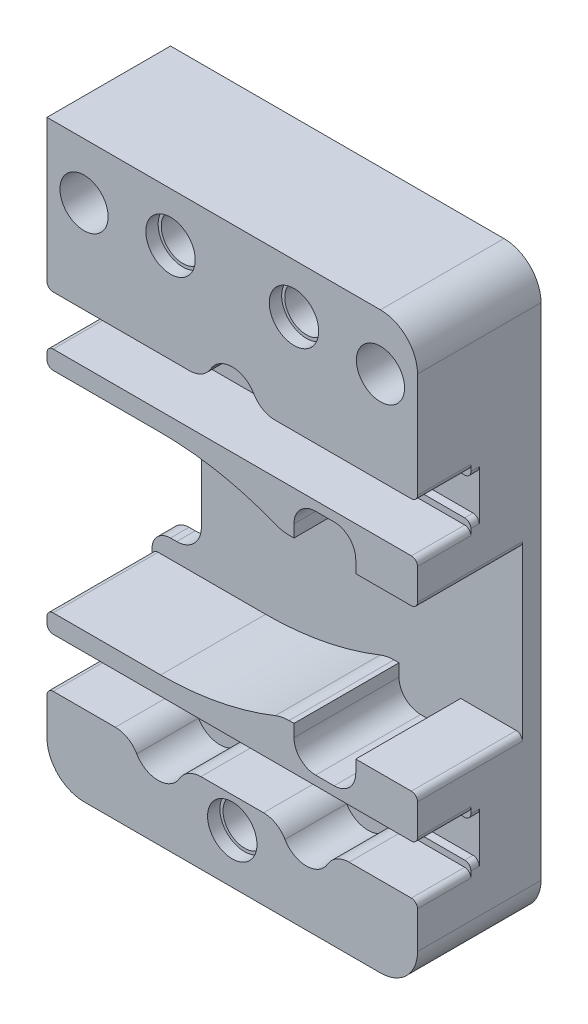
SolidWorks part; units mm, degrees
ref_plane "Front Plane" through (0, 0, 0) normal (0, 0, 1) x (1, 0, 0)
ref_plane "Top Plane" through (0, 0, 0) normal (0, 1, 0) x (1, 0, 0)
ref_plane "Right Plane" through (0, 0, 0) normal (1, 0, 0) x (0, 0, -1)
sketch "Sketch6" plane through (0, 0, 0) normal (0, 0, 1) x (1, 0, 0)
  line L1 (0, 0) -> (-30, 0)
  line L2 (0, 0) -> (0, 46.5)
  line L3 (0, 46.5) -> (-30, 46.5)
  line L4 (-30, 0) -> (-30, 46.5)
  dimension "D1" = 30
  dimension "D2" = 46.5
extrude "Boss-Extrude3" add sketch "Sketch6" along normal blind 10
sketch "Sketch7" plane through (0, 0, 0) normal (0, 0, 1) x (1, 0, 0)
  line L0 (-30, 0) -> (0, 0) construction
  line L1 (-50.5273, 13.5) -> (-28, 13.5)
  line L2 (-50.5273, 13.5) -> (-50.5273, 27.5)
  line L3 (-50.5273, 27.5) -> (-28, 27.5)
  line L4 (-26, 15.5) -> (-26, 25.5)
  line L6 (-30, 46.5) -> (-30, 0) construction
  arc A0 (-28, 13.5) -> (-26, 15.5) centre (-28, 15.5) ccw
  arc A1 (-28, 27.5) -> (-26, 25.5) centre (-28, 25.5) cw
  dimension "D1" = 2
  dimension "D5" = 2
  dimension "D2" = 13.5
  dimension "D3" = 4
  dimension "D4" = 14
extrude "Cut-Extrude2" cut sketch "Sketch7" along normal through all
sketch "Sketch9" plane through (0, 0, 10) normal (0, 0, 1) x (1, 0, 0)
  line L0 (-27, 42) -> (-3, 42) construction
  line L2 (-30, 0) -> (0, 0) construction
  line L3 (0, 46.5) -> (-30, 46.5) construction
  line L5 (-20, 42.5) -> (-10, 42.5) construction
  circle A0 centre (-10, 42.5) radius 4 construction
  circle A1 centre (-15, 4) radius 1.75 construction
  circle A2 centre (-3, 42) radius 1.95
  circle A3 centre (-27, 42) radius 1.95
  circle A4 centre (-15, 4) radius 2 construction
  circle A5 centre (-20, 42.5) radius 1.75 construction
  circle A6 centre (-10, 42.5) radius 1.75 construction
  circle A7 centre (-20, 42.5) radius 4 construction
  point P1 (-15, 42)
  point P7 (-15, 0)
  point P20 (-15, 46.5)
  point P24 (-15, 42.5)
  dimension "D1" = 3.9
  dimension "D4" = 3.5
  dimension "D6" = 4
  dimension "D8" = 8
  dimension "D2" = 42
  dimension "D3" = 24
  dimension "D5" = 4
  dimension "D7" = 10
  dimension "D9" = 4
extrude "Cut-Extrude4" cut sketch "Sketch9" against normal offset from surface (9 mm away) 1 up to face at (-22.7172, 21.6, 0)
fillet "Fillet1" radius 1.5 2 edges at (-30, 13.5, 5) (-30, 27.5, 5)
sketch "Sketch33" plane through (0, 0, 10) normal (0, 0, 1) x (1, 0, 0)
  line L0 (0, 0) -> (0, 46.5) construction
  line L1 (0, 34.5) -> (-11.5359, 34.5)
  line L2 (0, 34.5) -> (0, 30.5)
  line L3 (0, 30.5) -> (-30, 30.5)
  line L4 (-30, 34.5) -> (-30, 30.5)
  line L5 (-30, 46.5) -> (-30, 29) construction
  line L6 (-30, 12) -> (-30, 0) construction
  line L7 (0, 46.5) -> (-30, 46.5) construction
  line L8 (-30, 10.5) -> (-30, 6.5)
  line L9 (-18.4641, 34.5) -> (-30, 34.5)
  line L10 (0, 10.5) -> (0, 6.5)
  line L11 (-17.5359, 6.5) -> (-12.4641, 6.5)
  line L12 (-5.5359, 6.5) -> (0, 6.5)
  line L24 (0, 20.5) -> (-33.7301, 20.5) construction
  line L26 (-30, 6.5) -> (-24.4641, 6.5)
  line L27 (-30, 10.5) -> (0, 10.5)
  line L36 (-26, 15.5) -> (-26, 25.5) construction
  arc A0 (-13.2679, 35.5) -> (-16.7321, 35.5) centre (-15, 34.5) ccw
  arc A1 (-10.7321, 5.5) -> (-7.2679, 5.5) centre (-9, 6.5) ccw
  arc A2 (-13.2679, 35.5) -> (-11.5359, 34.5) centre (-11.5359, 36.5) ccw
  arc A3 (-16.7321, 35.5) -> (-18.4641, 34.5) centre (-18.4641, 36.5) cw
  arc A4 (-7.2679, 5.5) -> (-5.5359, 6.5) centre (-5.5359, 4.5) cw
  arc A5 (-10.7321, 5.5) -> (-12.4641, 6.5) centre (-12.4641, 4.5) ccw
  arc A6 (-17.5359, 6.5) -> (-19.2679, 5.5) centre (-17.5359, 4.5) ccw
  arc A7 (-24.4641, 6.5) -> (-22.7321, 5.5) centre (-24.4641, 4.5) cw
  arc A8 (-19.2679, 5.5) -> (-22.7321, 5.5) centre (-21, 6.5) cw
  point P14 (-30, 32.5)
  point P15 (-30, 8.5)
  point P17 (-15, 46.5)
  point P26 (-11.8223, 34.5)
  point P45 (-15, 6.5)
  point P49 (-26, 20.5)
  dimension "D5" = 2
  dimension "D4" = 2
  dimension "D6" = 2
  dimension "D1" = 12
  dimension "D2" = 12
  dimension "D3" = 4
  dimension "D7" = 12
extrude "Cut-Extrude24" cut sketch "Sketch33" against normal blind 5
fillet "Fillet13" radius 3 3 edges at (0, 0, 5) (-30, 0, 5) (0, 46.5, 5)
sketch "Sketch36" plane through (0, 0, 10) normal (0, 0, 1) x (1, 0, 0)
  line L0 (-10, 27) -> (-10, 14) construction
  line L1 (-10, 14) -> (-10, 13)
  line L2 (-10, 27) -> (-10, 28)
  line L3 (-11, 14) -> (-10, 14)
  line L4 (0, 14) -> (-5, 14)
  line L5 (0, 27) -> (0, 14)
  line L6 (-11, 14) -> (-13, 12)
  line L7 (-13, 29) -> (-11, 27)
  line L8 (-5, 27) -> (0, 27)
  line L9 (-10, 27) -> (-11, 27)
  line L10 (-5, 13) -> (-5, 14)
  line L11 (-5, 28) -> (-5, 27)
  line L12 (-30, 29) -> (-30, 12)
  line L13 (-13, 12) -> (-30, 12)
  line L14 (-13, 29) -> (-30, 29)
  line L15 (-8.25, 29.75) -> (-6.75, 29.75)
  line L17 (0, 10.5) -> (0, 30.5) construction
  line L18 (-8.25, 11.25) -> (-6.75, 11.25)
  line L19 (-30, 46.5) -> (-30, 34.5) construction
  arc A0 (-10, 28) -> (-8.25, 29.75) centre (-8.25, 28) cw
  arc A1 (-5, 28) -> (-6.75, 29.75) centre (-6.75, 28) ccw
  arc A2 (-5, 13) -> (-6.75, 11.25) centre (-6.75, 13) cw
  arc A3 (-10, 13) -> (-8.25, 11.25) centre (-8.25, 13) ccw
  point P0 (0, 20.5)
  dimension "D4" = 5
  dimension "D9" = 1.75
  dimension "D1" = 13
  dimension "D2" = 17
  dimension "D3" = 5
  dimension "D5" = 17
  dimension "D6" = 1
  dimension "D7" = 13
  dimension "D8" = 1
extrude "Cut-Extrude26" cut sketch "Sketch36" against normal blind 8.5
fillet "Fillet14" radius 25 2 edges at (-13, 12, 5.75) (-13, 29, 5.75)
sketch "Sketch37" plane through (0, 0, 10) normal (0, 0, 1) x (1, 0, 0)
  line L0 (-27, 0) -> (-3, 0) construction
  line L1 (-10, 42.5) -> (-20, 42.5) construction
  line L2 (-3, 46.5) -> (-30, 46.5) construction
  line L3 (-27, 42) -> (-27, 38.9009) construction
  line L4 (-3, 42) -> (-3, 38.389) construction
  line L5 (-15, 42.5) -> (-15, 40.1945) construction
  circle A0 centre (-20, 42.5) radius 1.75
  circle A1 centre (-10, 42.5) radius 1.75
  circle A2 centre (-15, 4) radius 1.75
  point P6 (-15, 0)
  point P11 (-15, 42.5)
  point P12 (-15, 46.5)
  dimension "D2" = 3.5
  dimension "D1" = 4
  dimension "D3" = 10
  dimension "D4" = 4
extrude "Cut-Extrude27" cut sketch "Sketch37" against normal blind 8.5
sketch "Sketch38" plane through (0, 0, 10) normal (0, 0, 1) x (1, 0, 0)
  circle A0 centre (-20, 42.5) radius 2
  circle A1 centre (-10, 42.5) radius 2
  circle A2 centre (-15, 4) radius 2
  dimension "D1" = 4
extrude "Cut-Extrude28" cut sketch "Sketch38" against normal blind 1
fillet "Fillet15" radius 0.5 8 edges at (-30, 6.5, 7.5) (-30, 10.5, 7.5) (0, 6.5, 7.5) (0, 10.5, 7.5) (0, 30.5, 7.5) (0, 34.5, 7.5) (-30, 30.5, 7.5) (-30, 34.5, 7.5)
fillet "Fillet16" radius 0.5 4 edges at (0, 27, 5.75) (0, 14, 5.75) (-30, 12, 5.75) (-30, 29, 5.75)
fillet "Fillet17" radius 3 2 edges at (-11, 14, 5.75) (-11, 27, 5.75)
sketch "Sketch39" plane through (0, 0, 1) normal (0, 0, 1) x (1, 0, 0)
  circle A0 centre (-27, 42) radius 1.5
  circle A1 centre (-3, 42) radius 1.5
  dimension "D1" = 3
extrude "Cut-Extrude29" cut sketch "Sketch39" against normal through all
sketch "Sketch40" plane through (0, 0, 5) normal (0, 0, 1) x (1, 0, 0)
  line L0 (0, 34) -> (-5, 34)
  line L1 (0, 30) -> (0, 35) construction
  line L2 (-5, 34) -> (-5, 34.5)
  line L3 (-0.5, 34.5) -> (-11.5359, 34.5) construction
  line L4 (-5, 34.5) -> (-0.5, 34.5)
  line L5 (0, 35) -> (0, 34)
  line L6 (-5, 30.5) -> (-5, 31)
  line L7 (-29.5, 30.5) -> (-0.5, 30.5) construction
  line L8 (-5, 31) -> (0, 31)
  line L9 (0, 31) -> (0, 30)
  line L10 (-5, 30.5) -> (-0.5, 30.5)
  line L11 (-2.5, 34) -> (-2.5, 31) construction
  line L12 (-0.5, 32.5) -> (-0.5, 34) construction
  line L13 (-15, 30.5) -> (-15, 10.5) construction
  line L14 (-29.5, 32.5) -> (-29.5, 34) construction
  line L15 (-27.5, 34) -> (-27.5, 31) construction
  line L16 (-25, 30.5) -> (-29.5, 30.5)
  line L17 (-30, 31) -> (-30, 30)
  line L18 (-25, 31) -> (-30, 31)
  line L19 (-25, 30.5) -> (-25, 31)
  line L20 (-30, 35) -> (-30, 34)
  line L21 (-25, 34.5) -> (-29.5, 34.5)
  line L22 (-25, 34) -> (-25, 34.5)
  line L23 (-30, 34) -> (-25, 34)
  line L24 (-0.5, 10.5) -> (-29.5, 10.5) construction
  line L25 (-15, 20.5) -> (-36.1363, 20.5) construction
  line L26 (-0.5, 8.5) -> (-0.5, 7) construction
  line L27 (-2.5, 7) -> (-2.5, 10) construction
  line L28 (-5, 10.5) -> (-0.5, 10.5)
  line L29 (0, 10) -> (0, 11)
  line L30 (-5, 10) -> (0, 10)
  line L31 (-5, 10.5) -> (-5, 10)
  line L32 (0, 6) -> (0, 7)
  line L33 (-5, 6.5) -> (-0.5, 6.5)
  line L34 (-5, 7) -> (-5, 6.5)
  line L35 (0, 7) -> (-5, 7)
  line L36 (-27.5, 7) -> (-27.5, 10) construction
  line L37 (-29.5, 8.5) -> (-29.5, 7) construction
  line L38 (-30, 7) -> (-25, 7)
  line L39 (-25, 7) -> (-25, 6.5)
  line L40 (-25, 6.5) -> (-29.5, 6.5)
  line L41 (-30, 6) -> (-30, 7)
  line L42 (-25, 10.5) -> (-25, 10)
  line L43 (-25, 10) -> (-30, 10)
  line L44 (-30, 10) -> (-30, 11)
  line L45 (-25, 10.5) -> (-29.5, 10.5)
  arc A0 (0, 35) -> (-0.5, 34.5) centre (-0.5, 35) cw
  arc A1 (-0.5, 30.5) -> (0, 30) centre (-0.5, 30) cw
  circle A2 centre (-2.5, 32.5) radius 2 construction
  circle A3 centre (-27.5, 32.5) radius 2 construction
  arc A4 (-29.5, 30.5) -> (-30, 30) centre (-29.5, 30) ccw
  arc A5 (-30, 35) -> (-29.5, 34.5) centre (-29.5, 35) ccw
  circle A6 centre (-2.5, 8.5) radius 2 construction
  arc A7 (-0.5, 10.5) -> (0, 11) centre (-0.5, 11) ccw
  arc A8 (0, 6) -> (-0.5, 6.5) centre (-0.5, 6) ccw
  circle A9 centre (-27.5, 8.5) radius 2 construction
  arc A10 (-30, 6) -> (-29.5, 6.5) centre (-29.5, 6) cw
  arc A11 (-29.5, 10.5) -> (-30, 11) centre (-29.5, 11) cw
  point P24 (-2.5, 32.5)
  point P25 (0, 32.5)
  point P30 (-1.1771, 34)
  point P52 (-28.8229, 34)
  point P53 (-30, 32.5)
  point P76 (-1.1771, 7)
  point P77 (0, 8.5)
  point P96 (-30, 8.5)
  point P97 (-28.8229, 7)
  dimension "D1" = 5
  dimension "D2" = 3
  dimension "D3" = 0.6771
extrude "Boss-Extrude4" add sketch "Sketch40" along normal blind 0.677
fillet "Fillet18" radius 1 8 edges at (-5, 6.5, 5.3385) (-5, 10.5, 5.3385) (-25, 6.5, 5.3385) (-25, 10.5, 5.3385) (-25, 34.5, 5.3385) (-25, 30.5, 5.3385) (-5, 30.5, 5.3385) (-5, 34.5, 5.3385)
fillet "Fillet19" radius 1 8 edges at (-25, 10, 5.3385) (-25, 7, 5.3385) (-5, 7, 5.3385) (-5, 10, 5.3385) (-5, 34, 5.3385) (-5, 31, 5.3385) (-25, 31, 5.3385) (-25, 34, 5.3385)
fillet "Fillet20" radius 0.5 8 edges at (-30, 7, 5.3385) (-30, 10, 5.3385) (-30, 34, 5.3385) (-30, 31, 5.3385) (0, 10, 5.3385) (0, 7, 5.3385) (0, 34, 5.3385) (0, 31, 5.3385)
